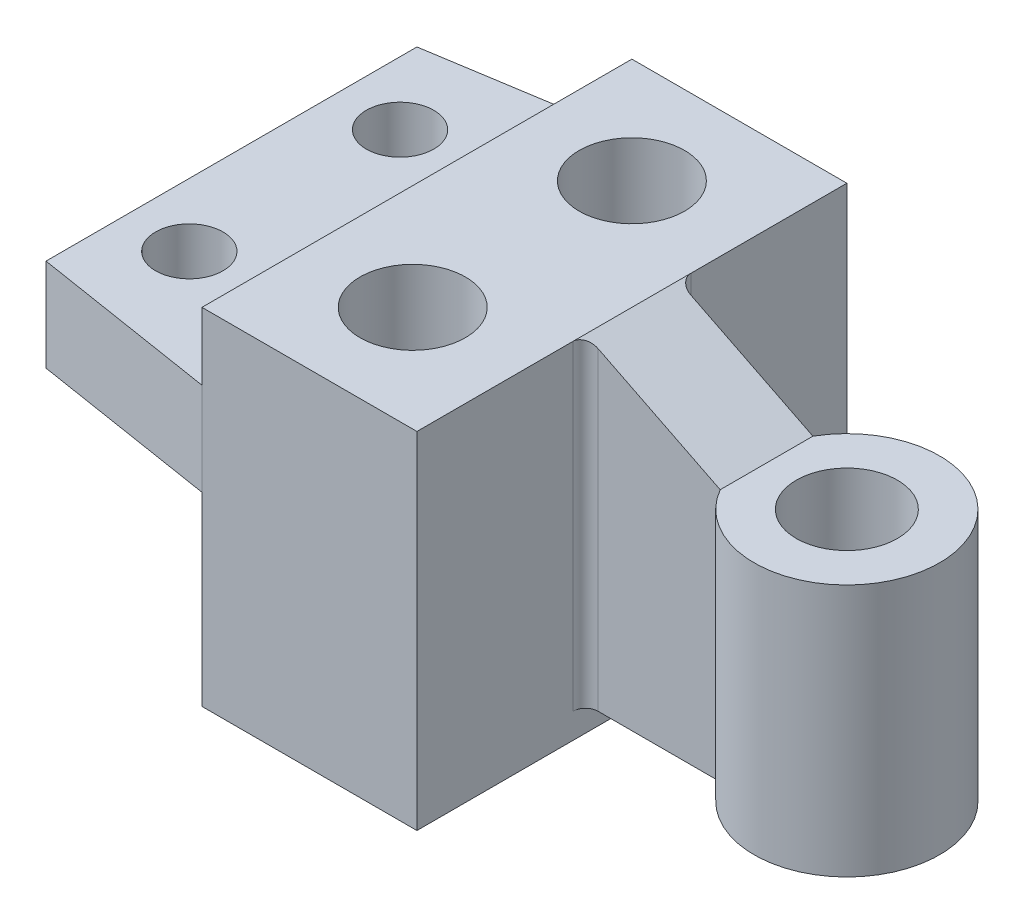
SolidWorks part; units mm, degrees
ref_plane "Piano frontale" through (0, 0, 0) normal (0, 0, 1) x (1, 0, 0)
ref_plane "Piano superiore" through (0, 0, 0) normal (0, 1, 0) x (1, 0, 0)
ref_plane "Piano destro" through (0, 0, 0) normal (1, 0, 0) x (0, 0, -1)
sketch "Schizzo1" plane through (0, 0, 0) normal (0, 1, 0) x (1, 0, 0)
  line L0 (0, 0) -> (238.3165, 0) construction
  line L1 (-25, 51) -> (26, 51)
  line L2 (-25, 51) -> (-25, -51)
  line L3 (-25, -51) -> (26, -51)
  line L4 (26, 51) -> (26, -51)
  line L5 (26, 11) -> (57.9474, 11)
  line L6 (57.9474, 11) -> (57.9474, -11)
  line L7 (26, -11) -> (57.9474, -11)
  line L8 (26, 11) -> (26, -11)
  circle A0 centre (77, 0) radius 22
  point P14 (57.9474, 0)
  dimension "D6" = 44
  dimension "D1" = 51
  dimension "D2" = 25
  dimension "D3" = 102
  dimension "D4" = 51
  dimension "D5" = 51
  dimension "D7" = 22
extrude "Estrusione-Estrusione2" add sketch "Schizzo1" along normal blind 82 contours L4 L1 L2 L3 L8 | L4 L0 A0 L5 | L0 L8 L7 A0 | L0 A0 L6 | A0 L0 L6 | L6 L0 A0 | L0 L6 A0 region at (40.9899, 0, -5.5889) region at (24.8596, 0, 5.5) region at (40.9899, 0, 5.5889) region at (56.7614, 0, -4.1645) region at (56.7614, 0, 4.1645) region at (77.6009, 0, -9.4907) region at (77.6009, 0, 9.4907)
sketch "Schizzo2" plane through (0, 0, 0) normal (0, -1, 0) x (1, 0, 0)
  line L0 (26, 11) -> (26, 51) construction
  line L1 (26, 30.134) -> (106.0862, 30.134)
  line L2 (26, 30.134) -> (26, -38.2228)
  line L3 (26, -38.2228) -> (106.0862, -38.2228)
  line L4 (106.0862, 30.134) -> (106.0862, -38.2228)
  line L5 (-25, -51) -> (26, -51) construction
  dimension "D1" = 68.3567
  dimension "D2" = 80.0862
  dimension "D3" = 12.7772
extrude "Taglio-Estrusione1" cut sketch "Schizzo2" against normal blind 6
sketch "Schizzo3" plane through (0, 82, 0) normal (0, 1, 0) x (1, 0, 0)
  line L0 (26, 51) -> (26, 11) construction
  line L1 (26, 37.057) -> (107.8996, 37.057)
  line L2 (26, 37.057) -> (26, -40.1878)
  line L3 (26, -40.1878) -> (107.8996, -40.1878)
  line L4 (107.8996, 37.057) -> (107.8996, -40.1878)
  line L5 (-25, 51) -> (26, 51) construction
  dimension "D1" = 13.943
  dimension "D2" = 77.2447
  dimension "D3" = 81.8996
extrude "Taglio-Estrusione4" cut sketch "Schizzo3" against normal blind 16
sketch "Schizzo5" plane through (0, 0, 11) normal (0, 0, 1) x (1, 0, 0)
  line L1 (57.9474, 66) -> (26, 82)
  line L2 (26, 82) -> (26, 66)
  line L3 (26, 66) -> (57.9474, 66) construction
  line L4 (26, 66) -> (26, 6) construction
  line L5 (26, 66) -> (57.9474, 66)
extrude "Estrusione-Estrusione3" add sketch "Schizzo5" against normal blind 22
sketch "Schizzo6" plane through (-25, 0, 0) normal (-1, 0, 0) x (0, 0, 1)
  line L0 (51, 82) -> (51, 0) construction
  line L1 (51, 66) -> (-51, 66)
  line L2 (51, 66) -> (51, 44)
  line L3 (51, 44) -> (-51, 44)
  line L4 (-51, 66) -> (-51, 44)
  line L5 (-51, 82) -> (-51, 0) construction
  line L6 (-51, 0) -> (51, 0) construction
  dimension "D1" = 44
  dimension "D2" = 22
extrude "Estrusione-Estrusione4" add sketch "Schizzo6" along normal blind 44
sketch "Schizzo7" plane through (0, 66, 0) normal (0, 1, 0) x (1, 0, 0)
  line L0 (-25, -51) -> (-69, -44)
  line L1 (-69, -51) -> (-25, -51) construction
  line L2 (-69, -51) -> (-69, 51) construction
  line L3 (-25, 51) -> (-69, 44)
  line L4 (-25, -51) -> (-69, -51)
  line L5 (-69, -51) -> (-69, -44)
  line L6 (-69, 44) -> (-69, 51)
  line L7 (-69, 51) -> (-25, 51)
  circle A0 centre (-54, -25) radius 8
  circle A1 centre (-54, 25) radius 8
  dimension "D6" = 16
  dimension "D1" = 88
  dimension "D2" = 7
  dimension "D3" = 15
  dimension "D4" = 50
  dimension "D5" = 26
extrude "Taglio-Estrusione5" cut sketch "Schizzo7" against normal through all
sketch "Schizzo8" plane through (0, 82, 0) normal (0, 1, 0) x (1, 0, 0)
  line L0 (-25, 51) -> (-25, -51) construction
  line L1 (-25, -51) -> (26, -51) construction
  circle A0 centre (0, -26) radius 12.5
  circle A1 centre (0, 26) radius 12.5
  point P4 (0, 0)
  point P5 (0, 0)
  dimension "D4" = 25
  dimension "D1" = 25
  dimension "D2" = 25
  dimension "D3" = 52
extrude "Taglio-Estrusione6" cut sketch "Schizzo8" against normal through all
sketch "Schizzo9" plane through (0, 66, 0) normal (0, 1, 0) x (1, 0, 0)
  circle A0 centre (77, 0) radius 12
  arc A1 (57.9474, -11) -> (57.9474, 11) centre (77, 0) ccw construction
  dimension "D1" = 24
extrude "Taglio-Estrusione7" cut sketch "Schizzo9" against normal through all
fillet "Raccordo1" radius 3 1 edges at (26, 44, -11)
fillet "Raccordo2" radius 3 1 edges at (26, 44, 11)
